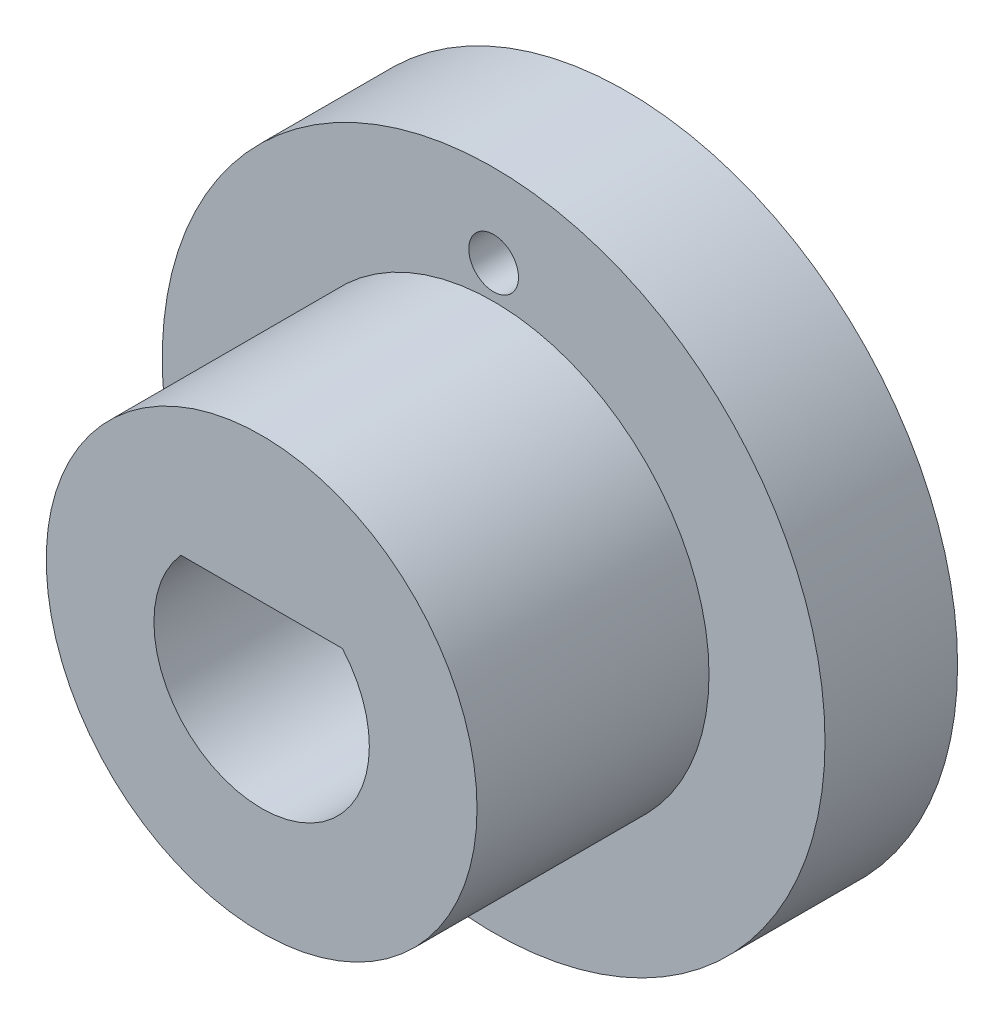
SolidWorks part; units mm, degrees
ref_plane "Plan de face" through (0, 0, 0) normal (0, 0, 1) x (1, 0, 0)
ref_plane "Plan de dessus" through (0, 0, 0) normal (0, 1, 0) x (1, 0, 0)
ref_plane "Plan de droite" through (0, 0, 0) normal (1, 0, 0) x (0, 0, -1)
sketch "Esquisse1" plane through (0, 0, 0) normal (0, 0, 1) x (1, 0, 0)
  line L8 (0, -7.5) -> (0, 7.5) construction
  circle A2 centre (0, -7.5) radius 0.75
  circle A3 centre (0, 7.5) radius 0.75
  circle A4 centre (0, 0) radius 10
  point P6 (0, 0)
  dimension "D2" = 1.5
  dimension "D3" = 1.5
  dimension "D4" = 20
  dimension "D1" = 15
extrude "Boss.-Extru.1" add sketch "Esquisse1" along normal blind 4
sketch "Esquisse2" [suppressed] plane through (0, 0, 10) normal (0, 0, 1) x (1, 0, 0)
  line L0 (-2.2, -2.0396) -> (-2.2, 2.0396)
  line L1 (3, -1.1913) -> (3, 1.3119) construction
  arc A0 (-2.2, -2.0396) -> (-2.2, 2.0396) centre (0, 0) ccw
  dimension "D1" = 6
  dimension "D2" = 5.2
extrude "Enlèv. mat.-Extru.1" [suppressed] cut sketch "Esquisse2" against normal offset from surface (8 mm away) 2 up to face at (10, 0, 0)
sketch "Esquisse3" plane through (0, 0, 4) normal (0, 0, 1) x (1, 0, 0)
  line L0 (-2.4372, 2.15) -> (2.4372, 2.15)
  line L1 (-0.8426, -3.25) -> (1.2459, -3.25) construction
  circle A0 centre (0, 0) radius 6.5
  arc A1 (-2.4372, 2.15) -> (2.4372, 2.15) centre (0, 0) ccw
  dimension "D1" = 6.5
  dimension "D3" = 13
  dimension "D2" = 5.4
extrude "Boss.-Extru.2" add sketch "Esquisse3" along normal blind 7
sketch "Esquisse5" plane through (0, 0, 4) normal (0, 0, 1) x (1, 0, 0)
  line L1 (2.4372, 2.15) -> (-2.4372, 2.15)
  line L2 (2.4372, 2.15) -> (-2.4372, 2.15)
  arc A1 (-2.4372, 2.15) -> (2.4372, 2.15) centre (0, 0) ccw
  arc A2 (-2.4372, 2.15) -> (2.4372, 2.15) centre (0, 0) ccw
  dimension "D1" = 0
extrude "Enlèv. mat.-Extru.2" cut sketch "Esquisse5" against normal offset from surface (2 mm away) 2 up to face at (10, 0, 0)
sketch "Esquisse4" plane through (0, 0, 0) normal (0, 0, -1) x (-1, 0, 0)
  line L1 (-4, 19) -> (4, 19)
  line L2 (-4, 19) -> (-4, -19)
  line L3 (-4, -19) -> (4, -19)
  line L4 (4, 19) -> (4, -19)
  point P4 (0, 19)
  point P5 (-4, 0)
  dimension "D1" = 8
  dimension "D2" = 38
extrude "Boss.-Extru.3" [suppressed] add sketch "Esquisse4" along normal blind 2
